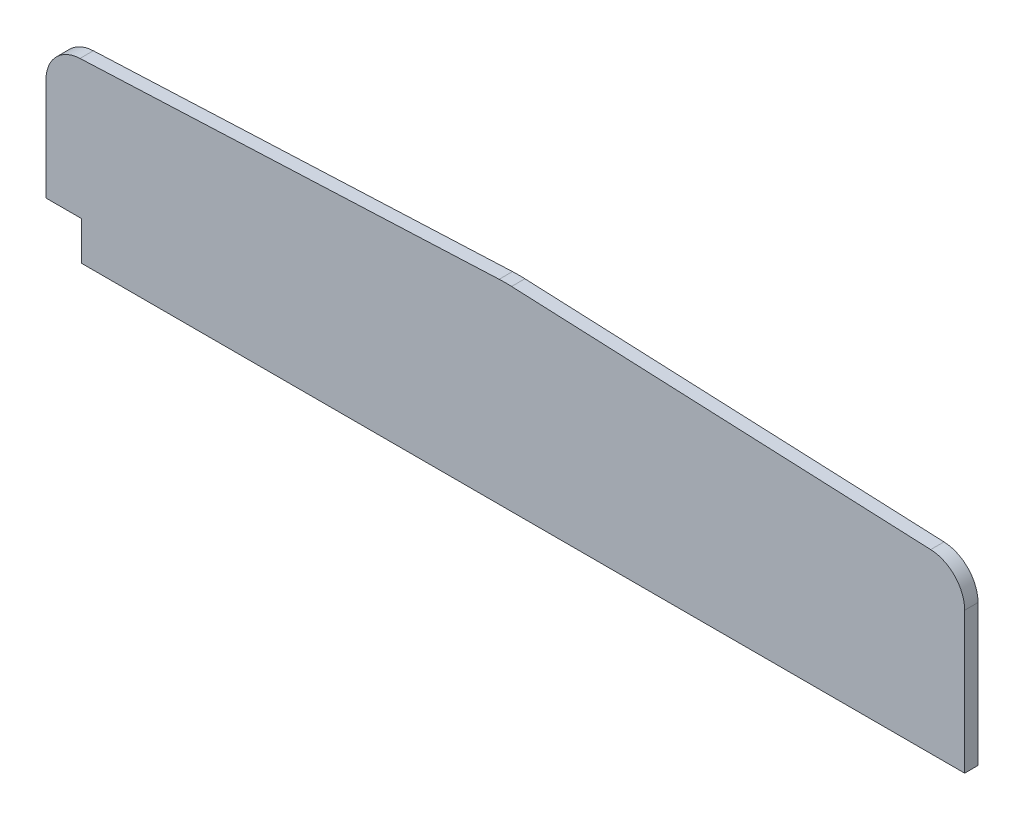
SolidWorks part; units mm, degrees
ref_plane "Front Plane" through (0, 0, 0) normal (0, 0, 1) x (1, 0, 0)
ref_plane "Top Plane" through (0, 0, 0) normal (0, 1, 0) x (1, 0, 0)
ref_plane "Right Plane" through (0, 0, 0) normal (1, 0, 0) x (0, 0, -1)
sketch "Sketch2" plane through (0, 0, 0) normal (0, 0, 1) x (1, 0, 0)
  line L0 (-328.3315, 55.6895) -> (-328.3315, 154.4895)
  line L1 (-328.3315, 154.4895) -> (0, 168.8465)
  line L2 (0, 168.8465) -> (328.2858, 154.4895)
  line L3 (328.2858, 154.4895) -> (328.2858, 55.6895)
  line L4 (328.2858, 55.6895) -> (328.2858, 29.2895)
  line L6 (328.2858, 29.2895) -> (-328.3315, 29.2895)
  line L7 (-328.3315, 29.2895) -> (-328.3315, 55.6895)
  dimension "D1" = 113.157
  dimension "D7" = 328.2858
  dimension "D8" = 98.8
  dimension "D9" = 26.4
extrude "Boss-Extrude1" add sketch "Sketch2" along normal mid plane 9.525
fillet "Fillet1" radius 25.4 2 edges at (328.2858, 154.4895, 0) (-328.3315, 154.4895, 0)
fillet "Fillet2" radius 101.6 1 edges at (0, 168.8465, 0)
sketch "Sketch3" plane through (0, 0, 4.7625) normal (0, 0, 1) x (1, 0, 0)
  line L0 (0, 0) -> (0, 192.0016) construction
  line L1 (-328.3315, 29.2895) -> (-302.9315, 29.2895)
  line L2 (-328.3315, 29.2895) -> (-328.3315, 56.9755)
  line L3 (-328.3315, 56.9755) -> (-302.9315, 56.9755)
  line L4 (-302.9315, 29.2895) -> (-302.9315, 56.9755)
  line L5 (0, 192.0016) -> (0, -60.0751) construction
  dimension "D1" = 25.4
  dimension "D2" = 27.686
extrude "Cut-Extrude1" cut sketch "Sketch3" against normal through all
